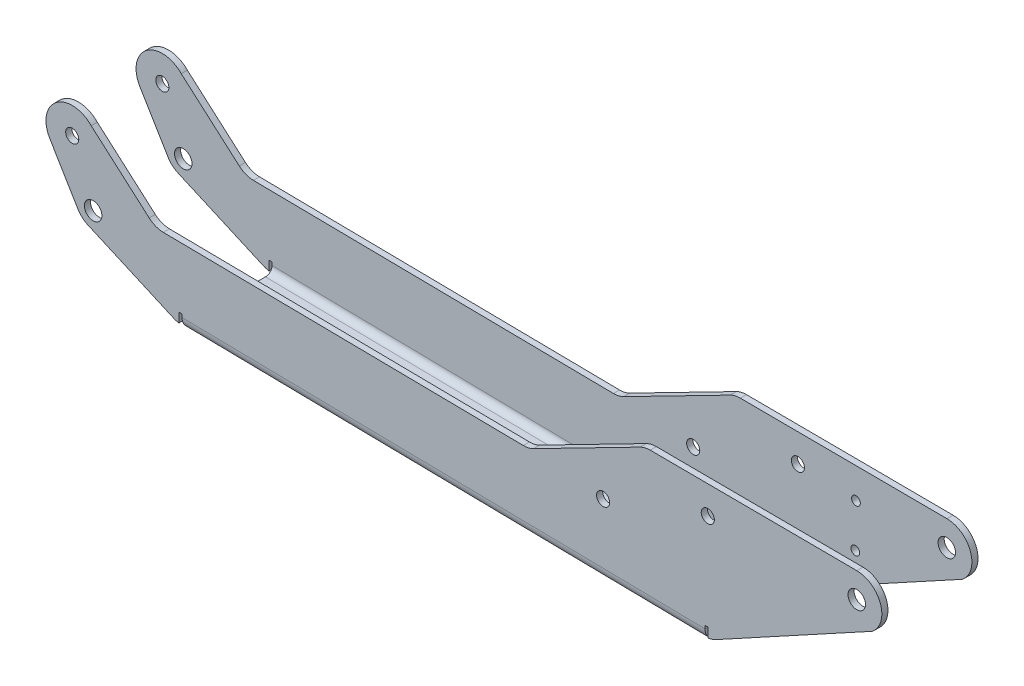
SolidWorks part; units mm, degrees
note: The reader was unsure of these and kept them because the rebuilt part matched: flange length of "Edge-Flange1".
ref_plane "Front Plane" through (0, 0, 0) normal (0, 0, 1) x (1, 0, 0)
ref_plane "Top Plane" through (0, 0, 0) normal (0, 1, 0) x (1, 0, 0)
ref_plane "Right Plane" through (0, 0, 0) normal (1, 0, 0) x (0, 0, -1)
sketch "Sketch2" plane through (0, 0, 0) normal (0, 0, 1) x (1, 0, 0)
  line L0 (110.8747, 169.3007) -> (232.868, 168.0195) construction
  line L1 (231.4782, 167.9235) -> (111.8685, 169.7952)
  line L2 (109.9284, 170.22) -> (90.3522, 178.8568)
  line L3 (88.0797, 180.8644) -> (81.6243, 191.6546)
  line L4 (91.1154, 198.8867) -> (104.3747, 187.2622)
  line L5 (107.6071, 186.0223) -> (189.9391, 184.9726)
  line L6 (192.2834, 185.5226) -> (216.6587, 198.016)
  line L7 (218.9657, 198.5663) -> (266.2136, 198.3172)
  line L8 (233.9522, 168.5343) -> (269.7006, 188.0491)
  arc A0 (266.2136, 198.3172) -> (269.7006, 188.0491) centre (266.1834, 192.5808) cw
  arc A1 (81.6243, 191.6546) -> (91.1154, 198.8867) centre (86.7764, 194.737) cw
  circle A2 centre (91.5684, 182.2893) radius 1.1478 construction
  circle A3 centre (86.7764, 194.737) radius 1.0668 construction
  circle A4 centre (232.1221, 192.0862) radius 0.8742 construction
  circle A5 centre (266.1834, 192.5808) radius 1.1755 construction
  arc A6 (189.9391, 184.9726) -> (192.2834, 185.5226) centre (190.0028, 189.9722) ccw
  arc A7 (216.6587, 198.016) -> (218.9657, 198.5663) centre (218.9393, 193.5664) cw
  arc A8 (233.9522, 168.5343) -> (231.4782, 167.9235) centre (231.5564, 172.9229) cw
  arc A9 (109.9284, 170.22) -> (111.8685, 169.7952) centre (111.9467, 174.7946) ccw
  arc A10 (107.6071, 186.0223) -> (104.3747, 187.2622) centre (107.6709, 191.0219) cw
  arc A11 (90.3522, 178.8568) -> (88.0797, 180.8644) centre (92.3704, 183.4313) cw
  circle A12 centre (245.4018, 191.4665) radius 0.7725 construction
  circle A13 centre (245.2646, 181.5408) radius 0.6658 construction
  circle A14 centre (208.1864, 183.5188) radius 1.0221 construction
  circle A15 centre (86.7764, 194.737) radius 1.5
  circle A16 centre (91.5684, 182.2893) radius 2
  circle A17 centre (208.1864, 183.5188) radius 1.5
  circle A18 centre (232.1221, 192.0862) radius 1.5
  circle A20 centre (266.1834, 192.5808) radius 2
  dimension "D2" = 4
  dimension "D3" = 3
  dimension "D4" = 3
  dimension "D5" = 4
  dimension "D6" = 3
base flange "Base-Flange1" sketch "Sketch2" thickness 1.4 reverse thickness direction no parameters "D1"=1.5
edge flange "Edge-Flange1" sketch "Sketch14" flange angle 90 flange length 9.6 flange position material outside bend radius 1.5 thickness 1.4 relief rectangular parameters "D6"=10
sketch "Sketch14" plane through (2.6837, 171.5037, -1.4) normal (-0.0156, -0.9999, 0) x (-0.9999, 0.0156, 0)
  line L2 (-228.8225, 0) -> (-228.8225, 9.6)
  line L3 (-228.8225, 9.6) -> (-109.1981, 9.6)
  line L4 (-109.1981, 9.6) -> (-109.1981, 0)
  line L7 (-109.1981, 0) -> (-228.8225, 0) construction
  line L8 (-109.1981, 0) -> (-228.8225, 0)
bend "EdgeBend1" bend radius 1.5 bend angle 90 parameters "D5"=1
mirror "Mirror1" about plane through (231.4563, 166.5237, -11) normal (0, 0, 1) of bodies 104
bend "MirrorBend1" bend radius 1.5 bend angle 90 parameters "D5"=2
sketch "Sketch17" plane through (0, 0, -22) normal (0, 0, -1) x (-1, 0, 0)
  circle A0 centre (-245.4018, 191.4665) radius 1
  circle A1 centre (-245.2646, 181.5408) radius 1
  dimension "D1" = 2
  dimension "D2" = 2
extrude "Cut-Extrude1" cut sketch "Sketch17" against normal blind 1.4 normal cut yes
ref_plane "Plane1" through (0, 0, -11) normal (0, 0, 1) x (1, 0, 0)
sketch "Bend-Lines3" [suppressed] plane through (0, 0, 0) normal (0, 1, 0) x (1, 0, 0)
sketch "Bounding-Box3" [suppressed] plane through (0, 0, 0) normal (0, 1, 0) x (1, 0, 0)
sheet metal parameters "Sheet-Metal3" thickness 1.4 parameters "D1"=1.5
flat pattern "Flat-Pattern3" [suppressed]
sketch "Bend-Lines4" plane through (0, 0, 0) normal (0, 1, 0) x (1, 0, 0)
sketch3d "Bounding-Box4" [suppressed]
  line L0 (-5.9222, 6.0843, 0) -> (185.2202, 3.5021, 0) construction
  line L1 (-6.339, -24.773, 0) -> (184.8033, -27.3552, 0) construction
  line L2 (-5.9222, 6.0843, 0) -> (-6.339, -24.773, 0) construction
  line L3 (185.2202, 3.5021, 0) -> (184.8033, -27.3552, 0) construction
sheet metal parameters "Sheet-Metal4" thickness 1.4 parameters "D1"=1.5
flat pattern "Flat-Pattern3"
sketch "Bend-Lines4" plane through (0, 0, 0) normal (0, 0, 1) x (1, 0, 0)
  line L0 (111.8649, 169.5673) -> (231.4746, 167.6957) construction
  line L1 (111.8649, 169.5673) -> (231.4746, 167.6957) construction
sketch3d "Bounding-Box4" [suppressed]
  line L0 (-5.9222, 6.0843, 0) -> (185.2202, 3.5021, 0) construction
  line L1 (-6.5073, -37.2276, 0) -> (184.6351, -39.8098, 0) construction
  line L2 (-5.9222, 6.0843, 0) -> (-6.5073, -37.2276, 0) construction
  line L3 (185.2202, 3.5021, 0) -> (184.6351, -39.8098, 0) construction
bend of the flat pattern "Flatten-<EdgeBend1>1"
sheet metal parameters "Sheet-Metal5" thickness 1.4 parameters "D1"=1.5
flat pattern "Flat-Pattern5"
sketch "Bend-Lines5" plane through (0, 0, 0) normal (0, 0, 1) x (1, 0, 0)
  line L0 (111.5573, 149.914) -> (231.1671, 148.0423) construction
  line L1 (111.8649, 169.5673) -> (231.4746, 167.6957) construction
  line L2 (111.5573, 149.914) -> (231.1671, 148.0423) construction
  line L3 (111.8649, 169.5673) -> (231.4746, 167.6957) construction
sketch3d "Bounding-Box5" [suppressed]
  line L0 (-5.9031, 6.4806, 0) -> (185.2323, 3.4897, 0) construction
  line L1 (-7.1858, -75.488, 0) -> (183.9497, -78.4789, 0) construction
  line L2 (-5.9031, 6.4806, 0) -> (-7.1858, -75.488, 0) construction
  line L3 (185.2323, 3.4897, 0) -> (183.9497, -78.4789, 0) construction
bend of the flat pattern "Flatten-<EdgeBend1>2"
bend of the flat pattern "Flatten-<MirrorBend1>1"
sheet metal parameters "Sheet-Metal6" thickness 1.4 parameters "D1"=1.5
flat pattern "Flat-Pattern5"
sketch "Bend-Lines5" plane through (0, 0, 0) normal (0, 0, 1) x (1, 0, 0)
  line L0 (111.5573, 149.914) -> (231.1671, 148.0423) construction
  line L1 (111.8649, 169.5673) -> (231.4746, 167.6957) construction
  line L2 (111.5573, 149.914) -> (231.1671, 148.0423) construction
  line L3 (111.8649, 169.5673) -> (231.4746, 167.6957) construction
sketch3d "Bounding-Box5" [suppressed]
  line L0 (-5.9031, 6.4806, 0) -> (185.2323, 3.4897, 0) construction
  line L1 (-7.1858, -75.488, 0) -> (183.9497, -78.4789, 0) construction
  line L2 (-5.9031, 6.4806, 0) -> (-7.1858, -75.488, 0) construction
  line L3 (185.2323, 3.4897, 0) -> (183.9497, -78.4789, 0) construction
bend of the flat pattern "Flatten-<EdgeBend1>2"
bend of the flat pattern "Flatten-<MirrorBend1>1"
